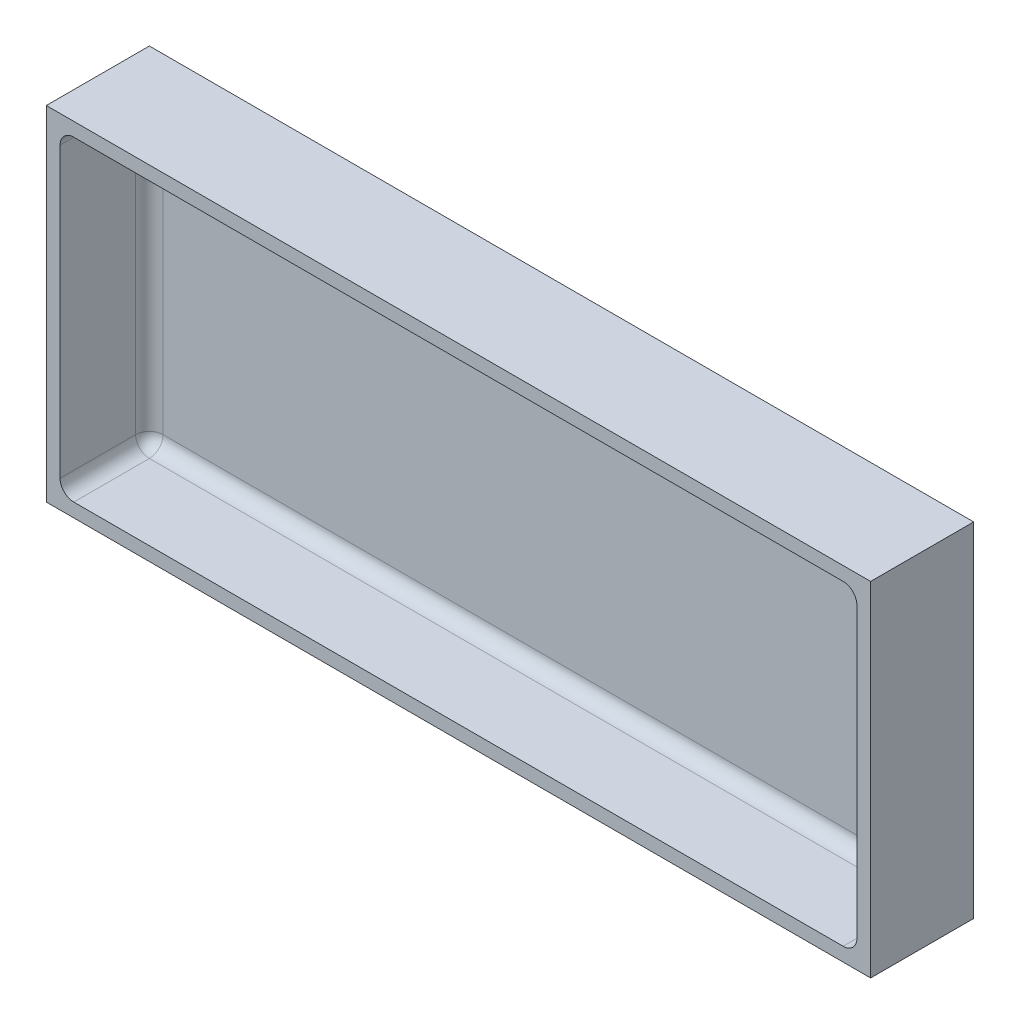
SolidWorks part; units mm, degrees
material "Alumina"
ref_plane "Front Plane" through (0, 0, 0) normal (0, 0, 1) x (1, 0, 0)
ref_plane "Top Plane" through (0, 0, 0) normal (0, 1, 0) x (1, 0, 0)
ref_plane "Right Plane" through (0, 0, 0) normal (1, 0, 0) x (0, 0, -1)
sketch "Sketch1" plane through (0, 0, 0) normal (0, 0, 1) x (1, 0, 0)
  line L1 (-60, -25) -> (60, -25)
  line L2 (-60, -25) -> (-60, 25)
  line L3 (-60, 25) -> (60, 25)
  line L4 (60, -25) -> (60, 25)
  line L5 (-60, -25) -> (60, 25) construction
  line L6 (-60, 25) -> (60, -25) construction
  point P0 (0, 0)
  dimension "D1" = 120
  dimension "D2" = 50
extrude "Boss-Extrude1" add sketch "Sketch1" against normal blind 15
shell "Shell1" thickness 2 removed face at (0, 0, 0)
fillet "Fillet1" radius 2 8 edges at (-58, 23, -6.5) (-58, -23, -6.5) (0, -23, -13) (-58, 0, -13) (0, 23, -13) (58, 0, -13) (58, 23, -6.5) (58, -23, -6.5)
